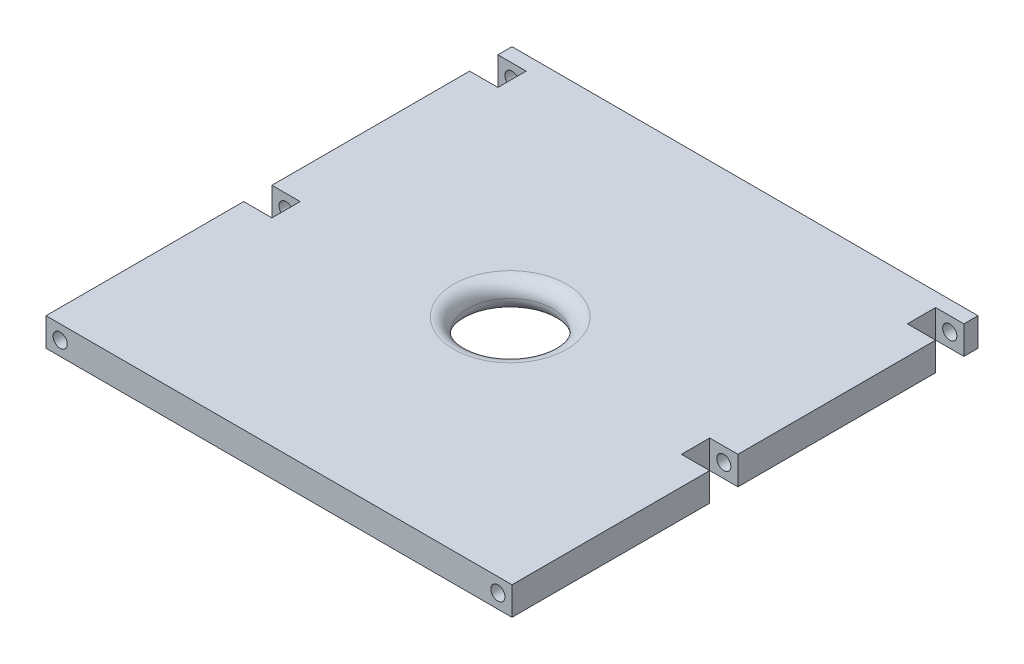
SolidWorks part; units mm, degrees
ref_plane "Plan de face" through (0, 0, 0) normal (0, 0, 1) x (1, 0, 0)
ref_plane "Plan de dessus" through (0, 0, 0) normal (0, 1, 0) x (1, 0, 0)
ref_plane "Plan de droite" through (0, 0, 0) normal (1, 0, 0) x (0, 0, -1)
sketch "Esquisse1" plane through (0, 0, 0) normal (0, 1, 0) x (1, 0, 0)
  line L0 (-82.5, 77.5) -> (-72.5, 77.5)
  line L1 (82.5, 82.5) -> (-82.5, 82.5)
  line L2 (82.5, 82.5) -> (82.5, 77.5)
  line L3 (82.5, -82.5) -> (-82.5, -82.5)
  line L4 (-82.5, 82.5) -> (-82.5, 77.5)
  line L5 (82.5, 82.5) -> (-82.5, -82.5) construction
  line L6 (82.5, -82.5) -> (-82.5, 82.5) construction
  line L7 (-72.5, 77.5) -> (-72.5, 67.5)
  line L8 (-72.5, 67.5) -> (-82.5, 67.5)
  line L9 (-82.5, -2.5) -> (-72.5, -2.5)
  line L10 (-72.5, -2.5) -> (-72.5, -12.5)
  line L11 (-72.5, -12.5) -> (-82.5, -12.5)
  line L12 (-82.5, -2.5) -> (-72.5, -12.5) construction
  line L13 (-72.5, -12.5) -> (-72.5448, -12.5817) construction
  line L14 (-82.5, 67.5) -> (-82.5, -2.5)
  line L15 (-82.5, -12.5) -> (-82.5, -82.5)
  line L16 (0, 16.0212) -> (0, -17.3175) construction
  line L17 (72.5, -12.5) -> (82.5, -12.5)
  line L18 (72.5, -2.5) -> (72.5, -12.5)
  line L19 (82.5, -2.5) -> (72.5, -2.5)
  line L20 (72.5, 77.5) -> (72.5, 67.5)
  line L21 (82.5, 77.5) -> (72.5, 77.5)
  line L22 (72.5, 67.5) -> (82.5, 67.5)
  line L23 (82.5, 67.5) -> (82.5, -2.5)
  line L24 (82.5, -12.5) -> (82.5, -82.5)
  circle A0 centre (0, -0.6481) radius 15
  point P0 (0, 0)
  point P12 (-77.5, -7.5)
  dimension "D9" = 30
  dimension "D1" = 165
  dimension "D2" = 165
  dimension "D3" = 5
  dimension "D4" = 10
  dimension "D5" = 10
  dimension "D6" = 10
  dimension "D7" = 10
  dimension "D8" = 90
extrude "BASE" add sketch "Esquisse1" along normal blind 10
sketch "Esquisse2" plane through (0, 0, -82.5) normal (0, 0, -1) x (-1, 0, 0)
  line L0 (-82.5, 5) -> (82.5, 5) construction
  line L1 (-82.5, 10) -> (-82.5, 0) construction
  line L2 (82.5, 10) -> (82.5, 0) construction
  line L3 (0, 17.3114) -> (0, -7.8072) construction
  circle A0 centre (-77.5, 5) radius 2.5
  circle A1 centre (77.5, 5) radius 2.5
  dimension "D1" = 5
  dimension "D2" = 5
extrude "VIDE VIS" cut sketch "Esquisse2" against normal through all
fillet "CONGE CABLE" radius 5 2 edges at (0, 0, 15.6481) (0, 10, 15.6481)
